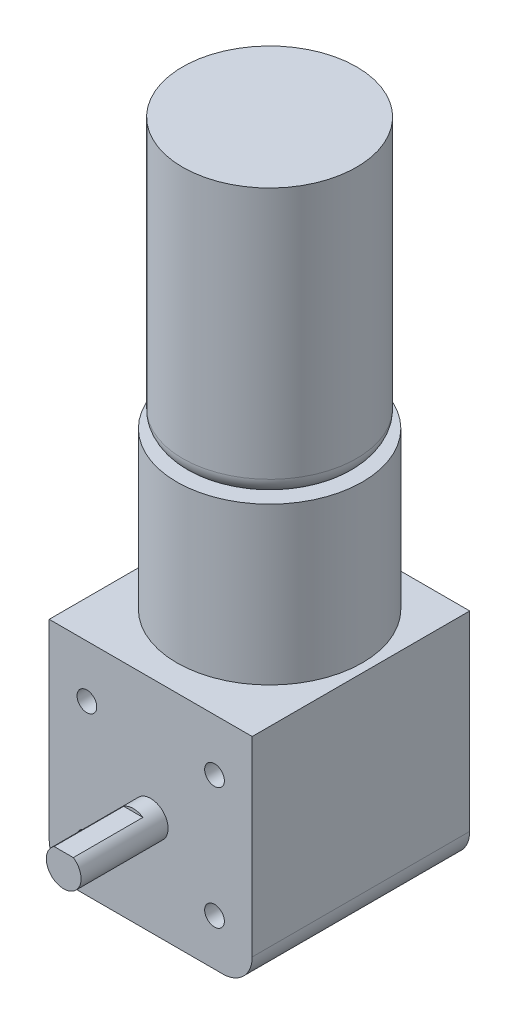
SolidWorks part; units mm, degrees
material "AISI 1010 Steel, hot rolled bar"
ref_plane "Front Plane" through (0, 0, 0) normal (0, 0, 1) x (1, 0, 0)
ref_plane "Top Plane" through (0, 0, 0) normal (0, 1, 0) x (1, 0, 0)
ref_plane "Right Plane" through (0, 0, 0) normal (1, 0, 0) x (0, 0, -1)
sketch "Sketch1" plane through (0, 0, 0) normal (0, 1, 0) x (1, 0, 0)
  line L1 (-17.5, 18.75) -> (17.5, 18.75)
  line L2 (-17.5, 18.75) -> (-17.5, -18.75)
  line L3 (-17.5, -18.75) -> (17.5, -18.75)
  line L4 (17.5, 18.75) -> (17.5, -18.75)
  line L5 (-17.5, 18.75) -> (17.5, -18.75) construction
  line L6 (-17.5, -18.75) -> (17.5, 18.75) construction
  point P0 (0, 0)
  dimension "D1" = 35
  dimension "D2" = 37.5
extrude "Boss-Extrude1" add sketch "Sketch1" against normal blind 38
sketch "Sketch2" plane through (0, 0, 0) normal (0, 1, 0) x (1, 0, 0)
  line L0 (-17.5, 17.75) -> (17.5, 17.75) construction
  line L1 (-17.5, 18.75) -> (-17.5, -18.75) construction
  line L2 (17.5, -18.75) -> (17.5, 18.75) construction
  line L3 (17.5, 18.75) -> (-17.5, 18.75) construction
  circle A0 centre (0, 1.75) radius 16
  dimension "D1" = 32
  dimension "D2" = 1
extrude "Boss-Extrude2" add sketch "Sketch2" along normal blind 27
sketch "Sketch3" plane through (0, 27, 0) normal (0, 1, 0) x (1, 0, 0)
  circle A0 centre (0, 1.75) radius 15
  dimension "D1" = 30
extrude "Boss-Extrude3" add sketch "Sketch3" along normal blind 46.5
sketch "Sketch7" plane through (0, 0, 0) normal (1, 0, 0) x (0, 0, -1)
  line L0 (1.75, 73.5) -> (1.75, 11.5842) construction
  line L1 (16.75, 73.5) -> (-13.25, 73.5) construction
  line L2 (16.75, 27) -> (16.75, 73.5) construction
  line L3 (17.75, 27) -> (-14.25, 27) construction
  line L4 (16.75, 27) -> (16.75, 73.5) construction
  line L5 (13.75, 27) -> (16.75, 27)
  line L6 (16.75, 27) -> (16.75, 73.5) construction
  line L7 (16.75, 27) -> (16.75, 30)
  arc A0 (16.75, 30) -> (13.75, 27) centre (13.75, 30) cw
  point P4 (13.75, 30)
  dimension "D1" = 3
  dimension "D2" = 3
revolve "Cut-Revolve2" cut sketch "Sketch7" angle 360 about L0
sketch "Sketch8" plane through (0, 0, 18.75) normal (0, 0, 1) x (1, 0, 0)
  line L0 (-17.5, 0) -> (17.5, 0) construction
  circle A0 centre (0, -21) radius 3
  dimension "D1" = 6
  dimension "D2" = 21
extrude "Boss-Extrude4" add sketch "Sketch8" along normal blind 15
sketch "Sketch9" plane through (0, 0, 18.75) normal (0, 0, 1) x (1, 0, 0)
  line L0 (-17.5, -38) -> (-17.5, 0) construction
  line L1 (-17.5, -38) -> (17.5, -38) construction
  line L2 (0, 0) -> (0, -12.644) construction
  point P0 (-11, -9)
  point P1 (-11, -30)
  point P9 (11, -30)
  point P10 (11, -9)
  dimension "D1" = 6.5
  dimension "D2" = 21
  dimension "D3" = 8
hole_wizard "M3 Clearance Hole1" positions "Sketch11" profile "Sketch10" hole size "M3" standard "ANSI Metric"
sketch "Sketch11" plane through (0, 0, 18.75) normal (0, 0, 1) x (1, 0, 0)
  point P0 (-11, -9)
  point P3 (11, -9)
  point P6 (11, -30)
  point P9 (-11, -30)
sketch "Sketch10" plane through (-11, -9, 18.75) normal (1, 0, 0) x (0, -1, 0)
  line L0 (0, 0) -> (0, 13.7215)
  line L1 (0, 13.7215) -> (1.7, 12.7)
  line L2 (1.7, 12.7) -> (1.7, 0)
  line L5 (1.7, 0) -> (0, 0)
  line L10 (0, 13.7215) -> (-1.7, 12.7) construction
  line L11 (0, -6.35) -> (0, 107.95) construction
  dimension "Hole Dia." = 3.4
  dimension "Hole Depth" = 12.7
  dimension "Drill Angle" = 118
fillet "Fillet1" radius 5.08 2 edges at (-17.5, -38, 0) (17.5, -38, 0)
sketch "Sketch12" plane through (0, 0, 33.75) normal (0, 0, 1) x (1, 0, 0)
  line L1 (-2.54, -18) -> (2.54, -18)
  line L2 (-2.54, -18) -> (-2.54, -18.5)
  line L3 (-2.54, -18.5) -> (2.54, -18.5)
  line L4 (2.54, -18) -> (2.54, -18.5)
  line L5 (-2.54, -18) -> (2.54, -18.5) construction
  line L6 (-2.54, -18.5) -> (2.54, -18) construction
  circle A0 centre (0, -21) radius 3 construction
  point P0 (0, -18.25)
  dimension "D1" = 0.5
  dimension "D2" = 5.08
extrude "Cut-Extrude1" cut sketch "Sketch12" against normal blind 12
